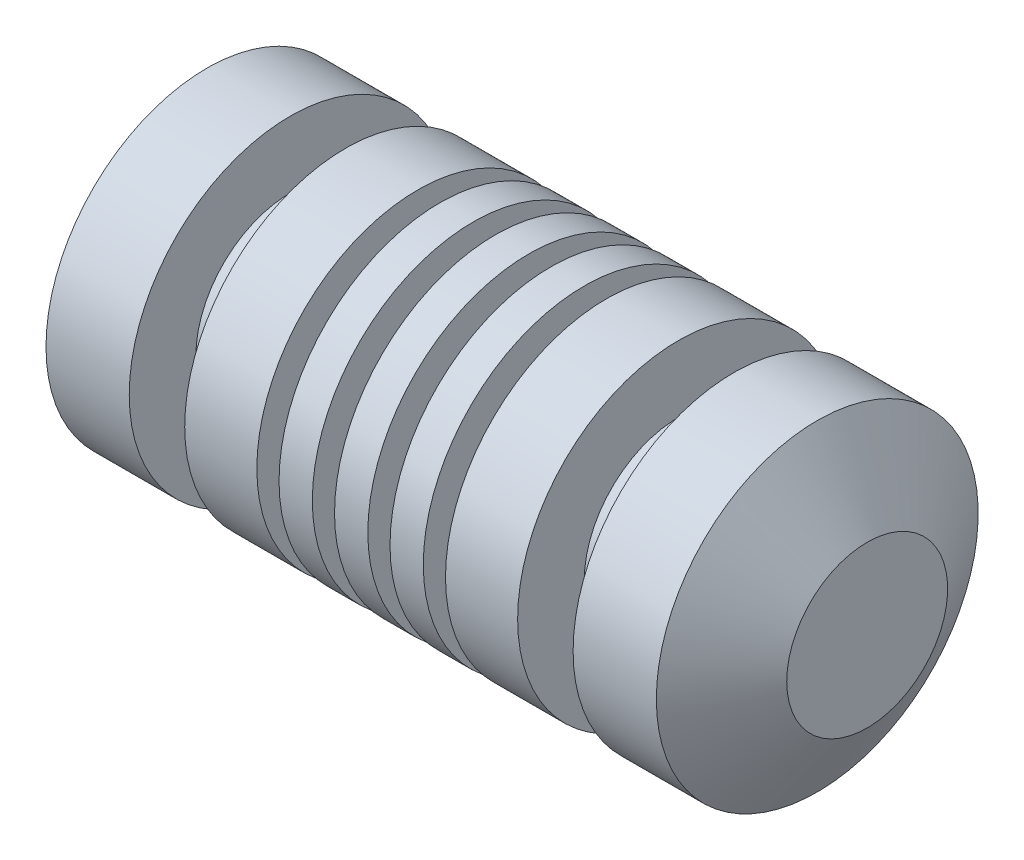
SolidWorks part; units mm, degrees
ref_plane "Front Plane" through (0, 0, 0) normal (0, 0, 1) x (1, 0, 0)
ref_plane "Top Plane" through (0, 0, 0) normal (0, 1, 0) x (1, 0, 0)
ref_plane "Right Plane" through (0, 0, 0) normal (1, 0, 0) x (0, 0, -1)
sketch "Sketch1" plane through (0, 0, 0) normal (0, 0, 1) x (1, 0, 0)
  line L0 (0, 0) -> (151.13, 0)
  line L40 (151.13, 18.415) -> (151.13, 0)
  line L42 (0, 36.83) -> (19.05, 36.83)
  line L43 (48.26, 36.83) -> (48.26, 29.21)
  line L44 (60.96, 36.83) -> (60.96, 29.21)
  line L45 (19.05, 36.83) -> (19.05, 21.59)
  line L46 (73.66, 36.83) -> (73.66, 29.21)
  line L48 (86.36, 36.83) -> (86.36, 29.21)
  line L49 (107.95, 36.83) -> (107.95, 21.59)
  line L50 (31.75, 36.83) -> (31.75, 21.59)
  line L52 (53.34, 36.83) -> (53.34, 29.21)
  line L53 (139.7, 36.83) -> (151.13, 18.415)
  line L54 (120.65, 36.83) -> (120.65, 21.59)
  line L55 (19.05, 21.59) -> (31.75, 21.59)
  line L56 (66.04, 36.83) -> (66.04, 29.21)
  line L57 (78.74, 36.83) -> (78.74, 29.21)
  line L58 (91.44, 36.83) -> (91.44, 29.21)
  line L59 (48.26, 29.21) -> (53.34, 29.21)
  line L60 (107.95, 21.59) -> (120.65, 21.59)
  line L61 (53.34, 36.83) -> (60.96, 36.83)
  line L62 (60.96, 29.21) -> (66.04, 29.21)
  line L63 (66.04, 36.83) -> (73.66, 36.83)
  line L64 (73.66, 29.21) -> (78.74, 29.21)
  line L65 (78.74, 36.83) -> (86.36, 36.83)
  line L66 (86.36, 29.21) -> (91.44, 29.21)
  line L67 (91.44, 36.83) -> (107.95, 36.83)
  line L68 (31.75, 36.83) -> (48.26, 36.83)
  line L69 (120.65, 36.83) -> (139.7, 36.83)
  line L70 (0, 36.83) -> (0, 0)
  dimension "D4" = 36.83
  dimension "D1" = 151.13
revolve "Revolve5" add sketch "Sketch1" angle 360 about L0
